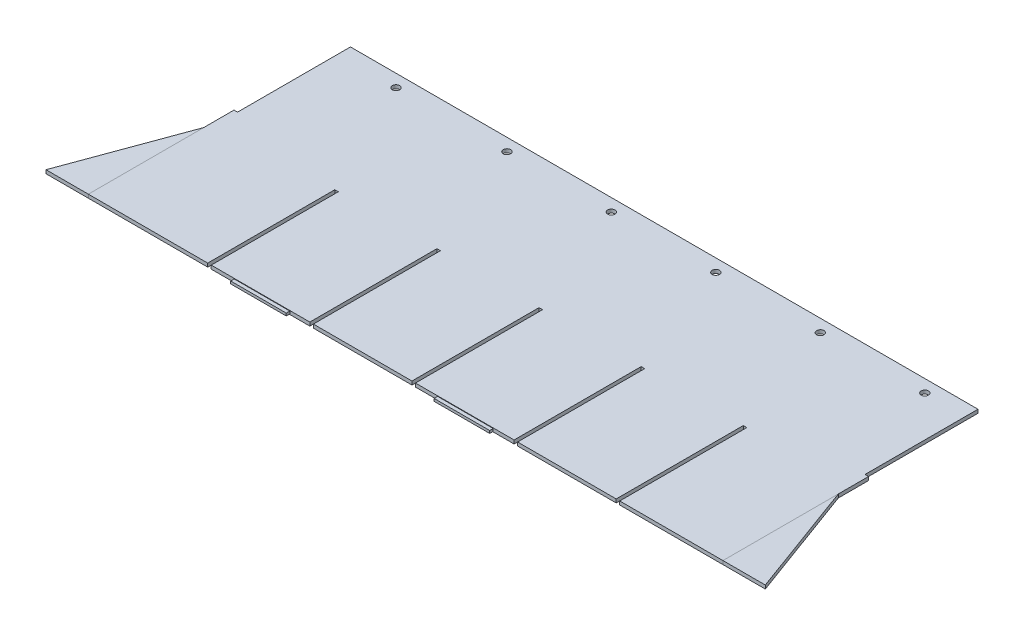
SolidWorks part; units mm, degrees
material "Custom Plastic"
ref_plane "X-Y Datum" through (0, 0, 0) normal (0, 0, 1) x (1, 0, 0)
ref_plane "X-Z Datum" through (0, 0, 0) normal (0, 1, 0) x (1, 0, 0)
ref_plane "Y-Z Datum" through (0, 0, 0) normal (1, 0, 0) x (0, 0, -1)
sketch "Sketch1" plane through (0, 0, 0) normal (0, 0, 1) x (1, 0, 0)
  line L1 (-285.4305, -1.5875) -> (285.4305, -1.5875)
  line L2 (-285.4305, -1.5875) -> (-285.4305, 1.5875)
  line L3 (-285.4305, 1.5875) -> (285.4305, 1.5875)
  line L4 (285.4305, -1.5875) -> (285.4305, 1.5875)
  line L5 (-285.4305, -1.5875) -> (285.4305, 1.5875) construction
  line L6 (-285.4305, 1.5875) -> (285.4305, -1.5875) construction
  point P0 (0, 0)
  dimension "D1" = 570.861
  dimension "D2" = 3.175
extrude "Boss-Extrude1" add sketch "Sketch1" along normal blind 232.6
sketch "Sketch2" plane through (0, 1.5875, 0) normal (0, 1, 0) x (1, 0, 0)
  line L0 (-176.5505, -128.8578) -> (-285.4305, -128.8578) construction
  line L1 (-285.4305, -232.6) -> (-285.4305, 0) construction
  line L3 (285.4305, -232.6) -> (-285.4305, -232.6) construction
  line L4 (-178.0615, -232.6) -> (-174.8865, -232.6)
  line L6 (-178.0615, -118.3) -> (-174.8865, -118.3)
  line L8 (-178.0615, -232.6) -> (-174.8865, -232.6)
  line L9 (-178.0615, -232.6) -> (-178.0615, -118.3)
  line L10 (-178.0615, -118.3) -> (-174.8865, -118.3)
  line L11 (-174.8865, -232.6) -> (-174.8865, -118.3)
  line L17 (-178.0615, -118.3) -> (-174.8865, -118.3)
  line L32 (-285.4305, -232.6) -> (-323.5305, -232.6)
  line L33 (-323.5305, -232.6) -> (-285.4305, -128.8578)
  line L34 (285.4305, -232.6) -> (323.5305, -232.6)
  line L35 (323.5305, -232.6) -> (285.4305, -128.8578)
  line L36 (-285.4305, -128.8578) -> (-285.4305, -232.6)
  line L37 (285.4305, -128.8578) -> (285.4305, -232.6)
  line L38 (-285.4305, 0) -> (-282.2555, 0)
  line L39 (-285.4305, 0) -> (-285.4305, -101.6)
  line L40 (-285.4305, -101.6) -> (-282.2555, -101.6)
  line L41 (-282.2555, 0) -> (-282.2555, -101.6)
  line L42 (285.4305, 0) -> (282.2555, 0)
  line L43 (285.4305, 0) -> (285.4305, -101.6)
  line L44 (285.4305, -101.6) -> (282.2555, -101.6)
  line L45 (282.2555, 0) -> (282.2555, -101.6)
  line M3 (285.4305, 0) -> (-285.4305, 0)
  line M4 (-285.4305, 0) -> (-285.4305, -232.6)
  line M5 (-285.4305, -232.6) -> (285.4305, -232.6)
  line M6 (285.4305, -232.6) -> (285.4305, 0)
  dimension "D1" = 107.369
  dimension "D2" = 103.7422
  dimension "D3" = 3.175
  dimension "D5" = 38.1
  dimension "D6" = 3.175
  dimension "D7" = 101.6
  dimension "D4" = 114.3
  dimension "D8" = 3.175
  dimension "D9" = 101.6
  dimension "D10" = 103.7422
  dimension "D11" = 38.1
extrude "Cut-Extrude1" cut sketch "Sketch2" against normal blind 3.175 contours L11 L6 L9 M5 region at (-176.474, 1.5875, 175.45)
sketch "Sketch6" plane through (0, 0, 232.6) normal (0, 0, 1) x (1, 0, 0)
  line L14 (78.762, -1.143) -> (78.762, 1.143)
  line L15 (28.762, 1.143) -> (78.762, 1.143)
  line L16 (28.762, -1.143) -> (78.762, 1.143) construction
  line L17 (28.762, 1.143) -> (78.762, -1.143) construction
  line L18 (28.762, -1.143) -> (78.762, -1.143)
  line L19 (28.762, -1.143) -> (28.762, 1.143)
  line L20 (-104.238, -1.143) -> (-104.238, 1.143)
  line L21 (-154.238, 1.143) -> (-104.238, 1.143)
  line L22 (-154.238, -1.143) -> (-104.238, 1.143) construction
  line L23 (-154.238, 1.143) -> (-104.238, -1.143) construction
  line L24 (-154.238, -1.143) -> (-104.238, -1.143)
  line L25 (-154.238, -1.143) -> (-154.238, 1.143)
  point P6 (237.7325, 0)
  dimension "D2" = 50
sketch "Sketch7" plane through (0, -1.5875, 0) normal (0, -1, 0) x (-1, 0, 0)
  line L1 (-285.4305, -232.6) -> (-285.4305, 0) construction
  circle A2 centre (-245.6805, -11.2916) radius 3.302
  dimension "D1" = 39.75
  dimension "D2" = 6.604
extrude "Cut-Extrude4" cut sketch "Sketch7" against normal through all contours A2 region at (245.6805, -1.5875, 11.2916)
extrude "Boss-Extrude2" add sketch "Sketch6" along normal blind 3.175
pattern_linear "LPattern1" count 5 spacing 93.98 along (-1, 0, 0) of "Cut-Extrude4"
extrude "Boss-Extrude4" add sketch "Sketch2<3>" against normal blind 3.175 separate body contours L33 L32 M4 | L34 L35 M6 region at (-298.1305, 1.5875, 198.0193) region at (298.1305, 1.5875, 198.0193)
sketch "Sketch2<3>" plane through (0, 1.5875, 0) normal (0, 1, 0) x (1, 0, 0) same geometry as "Sketch2"
pattern_linear "LPattern2" count 5 spacing 91.866 along (1, 0, 0) of "Cut-Extrude1"
extrude "Cut-Extrude5" cut sketch "Sketch2<4>" against normal through all contours L41 L40 M3 M4 | L45 L44 M3 M6 region at (283.843, 1.5875, 50.8) region at (-283.843, 1.5875, 50.8)
sketch "Sketch2<4>" plane through (0, 1.5875, 0) normal (0, 1, 0) x (1, 0, 0) same geometry as "Sketch2"
sketch "Sketch8" plane through (0, -1.5875, 0) normal (0, -1, 0) x (1, 0, 0)
  line L0 (-282.2555, 0) -> (282.2555, 0) construction
  line L1 (255.4605, 0) -> (207.4496, 0)
  line L2 (256.429, 61.9588) -> (256.429, 211.5258)
  line L4 (208.4181, 61.9588) -> (208.4181, 211.5258)
  line L5 (256.429, 61.9588) -> (208.4181, 61.9588)
  line L6 (285.4305, 0) -> (285.4305, 101.6) construction
  line L8 (256.429, 136.7423) -> (208.4181, 136.7423) construction
  line L9 (211.4551, 100.0588) -> (251.4551, 100.0588) construction
  line L11 (251.4551, 120.0588) -> (211.4551, 120.0588) construction
  line L12 (251.4551, 120.0588) -> (251.4551, 80.0588) construction
  line L13 (251.4551, 80.0588) -> (211.4551, 80.0588) construction
  line L14 (211.4551, 120.0588) -> (211.4551, 80.0588) construction
  line L15 (231.4551, 120.0588) -> (231.4551, 80.0588) construction
  line L16 (231.4551, 100.0588) -> (217.2925, 85.9371) construction
  line L21 (223.1996, 120.0707) -> (211.467, 108.3719) construction
  line L22 (211.467, 108.3719) -> (211.4431, 91.8034)
  line L27 (211.4431, 91.8034) -> (223.1419, 80.0708) construction
  line L28 (223.1419, 80.0708) -> (239.7105, 80.0469)
  line L33 (239.7105, 80.0469) -> (251.4431, 91.7457) construction
  line L35 (251.4431, 91.7457) -> (251.467, 108.3142)
  line L38 (251.467, 108.3142) -> (239.7682, 120.0468) construction
  line L39 (239.7682, 120.0468) -> (223.1996, 120.0707)
  line L45 (217.2925, 85.9371) -> (211.4551, 80.0588) construction
  line L46 (231.4551, 100.0588) -> (217.3333, 114.2213) construction
  line L47 (217.3333, 114.2213) -> (211.4551, 120.0588) construction
  line L48 (231.4551, 138.1588) -> (231.4551, 135.3258) construction
  line L49 (231.4551, 100.0588) -> (245.6176, 114.1805) construction
  line L50 (245.6176, 114.1805) -> (251.4551, 120.0588) construction
  line L51 (231.4551, 100.0588) -> (245.5768, 85.8963) construction
  line L52 (245.5768, 85.8963) -> (251.4551, 80.0588) construction
  line L53 (245.5768, 187.5883) -> (251.4551, 193.4258) construction
  line L54 (231.4551, 173.4258) -> (245.5768, 187.5883) construction
  line L56 (245.6176, 159.3041) -> (251.4551, 153.4258) construction
  line L57 (231.4551, 173.4258) -> (245.6176, 159.3041) construction
  line L58 (217.3333, 159.2633) -> (211.4551, 153.4258) construction
  line L59 (231.4551, 173.4258) -> (217.3333, 159.2633) construction
  line L60 (217.2925, 187.5475) -> (211.4551, 193.4258) construction
  line L61 (251.467, 165.1704) -> (239.7682, 153.4378) construction
  line L62 (239.7105, 193.4377) -> (251.4431, 181.7389) construction
  line L63 (211.4431, 181.6812) -> (223.1419, 193.4138) construction
  line L64 (223.1996, 153.4139) -> (211.467, 165.1127) construction
  line L65 (231.4551, 173.4258) -> (217.2925, 187.5475) construction
  line L66 (231.4551, 153.4258) -> (231.4551, 193.4258) construction
  line L67 (211.4551, 153.4258) -> (211.4551, 193.4258) construction
  line L68 (251.4551, 193.4258) -> (211.4551, 193.4258) construction
  line L69 (251.4551, 153.4258) -> (251.4551, 193.4258) construction
  line L70 (251.4551, 153.4258) -> (211.4551, 153.4258) construction
  line L71 (211.4551, 173.4258) -> (251.4551, 173.4258) construction
  line L72 (239.7682, 153.4378) -> (223.1996, 153.4139)
  line L73 (251.4431, 181.7389) -> (251.467, 165.1704)
  line L74 (223.1419, 193.4138) -> (239.7105, 193.4377)
  line L75 (211.467, 165.1127) -> (211.4431, 181.6812)
  line L76 (256.429, 211.5258) -> (208.4181, 211.5258)
  circle A10 centre (231.4551, 100.0588) radius 20 construction
  circle A11 centre (214.3738, 82.9979) radius 2
  circle A12 centre (248.5159, 82.9775) radius 2
  circle A13 centre (214.3942, 117.14) radius 2
  circle A14 centre (248.5363, 117.1196) radius 2
  circle A15 centre (231.4551, 173.4258) radius 20 construction
  circle A16 centre (248.5363, 156.365) radius 2
  circle A17 centre (214.3942, 156.3446) radius 2
  circle A18 centre (248.5159, 190.5071) radius 2
  circle A19 centre (214.3738, 190.4867) radius 2
  dimension "D6" = 4
  dimension "D7" = 4
  dimension "D8" = 4
  dimension "D9" = 4
  dimension "D1" = 29.0015
  dimension "D2" = 48.0109
  dimension "D3" = 40
  dimension "D4" = 40
  dimension "D5" = 40
extrude "Cut-Extrude6" [suppressed] cut sketch "Sketch8" against normal blind 2.54 contours A13 | A12 | A19 | A18 | A17 | A16 | A14 | A11
pattern_linear "LPattern3" [suppressed] count 5 spacing 90.17 of bodies 133
sketch "Sketch10" plane through (0, -1.5875, 0) normal (0, -1, 0) x (1, 0, 0)
  circle A0 centre (254.1685, 104.6371) radius 2
  circle A1 centre (207.0974, 104.6371) radius 2
extrude "Cut-Extrude7" [suppressed] cut sketch "Sketch10" against normal through all
sketch "Sketch11" plane through (0, -1.5875, 0) normal (0, -1, 0) x (1, 0, 0)
  line L0 (-282.2555, 0) -> (-282.2555, 101.6) construction
  circle A0 centre (-230.0055, 11.2916) radius 3.302
  dimension "D1" = 52.25
extrude "Cut-Extrude8" cut sketch "Sketch11" against normal through all and the other way through all contours A0 region at (-230.0055, -1.5875, 11.2916)
